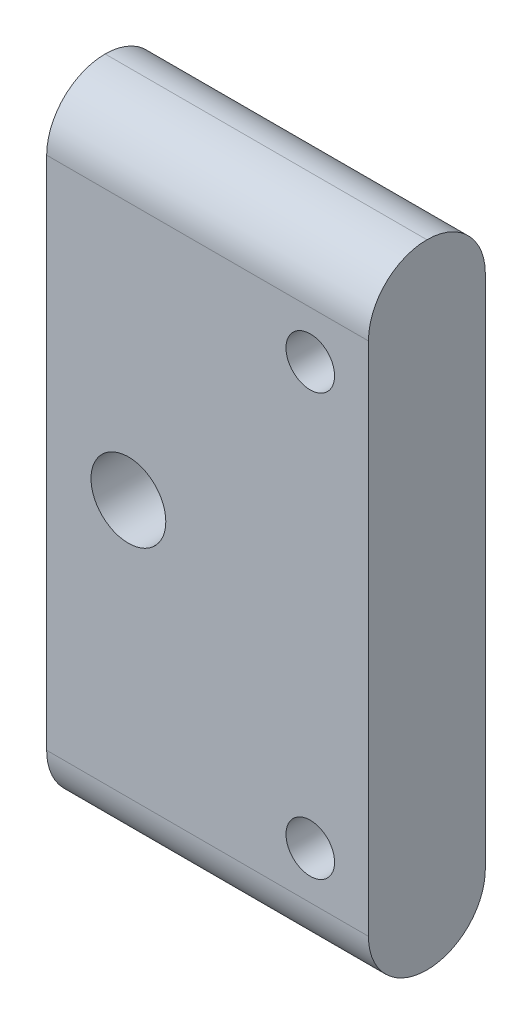
SolidWorks part; units mm, degrees
ref_plane "Front Plane" through (0, 0, 0) normal (0, 0, 1) x (1, 0, 0)
ref_plane "Top Plane" through (0, 0, 0) normal (0, 1, 0) x (1, 0, 0)
ref_plane "Right Plane" through (0, 0, 0) normal (1, 0, 0) x (0, 0, -1)
sketch "Sketch1" plane through (0, 0, 0) normal (0, 0, 1) x (1, 0, 0)
  line L0 (174.8184, 88.3592) -> (131.1184, 88.3896)
  line L1 (131.1184, 174.2592) -> (174.8184, 174.2592)
  line L2 (131.1184, 88.3896) -> (131.1184, 174.2592) construction
  line L3 (131.1184, 88.3896) -> (131.1184, 174.2592)
  line L4 (174.8184, 174.2592) -> (174.8184, 88.3592)
  line L5 (137.5548, 131.3092) -> (146.8816, 131.3092) construction
  line L6 (137.5548, 131.3092) -> (139.8865, 135.3478) construction
  line L7 (139.8865, 127.2706) -> (137.5548, 131.3092) construction
  line L8 (144.5499, 127.2706) -> (139.8865, 127.2706) construction
  line L9 (146.8816, 131.3092) -> (144.5499, 127.2706) construction
  line L10 (144.5499, 135.3478) -> (146.8816, 131.3092) construction
  line L11 (139.8865, 135.3478) -> (144.5499, 135.3478) construction
  circle A0 centre (166.9184, 159.9092) radius 3.3
  circle A1 centre (166.9184, 102.7092) radius 3.3
  circle A4 centre (142.2182, 131.3092) radius 5.08
extrude "Extrude1" add sketch "Sketch1" against normal blind 15.875
fillet "Fillet1" radius 7.9375 4 edges at (152.9684, 88.3744, -15.875) (152.9684, 88.3744, 0) (152.9684, 174.2592, -15.875) (152.9684, 174.2592, 0)
